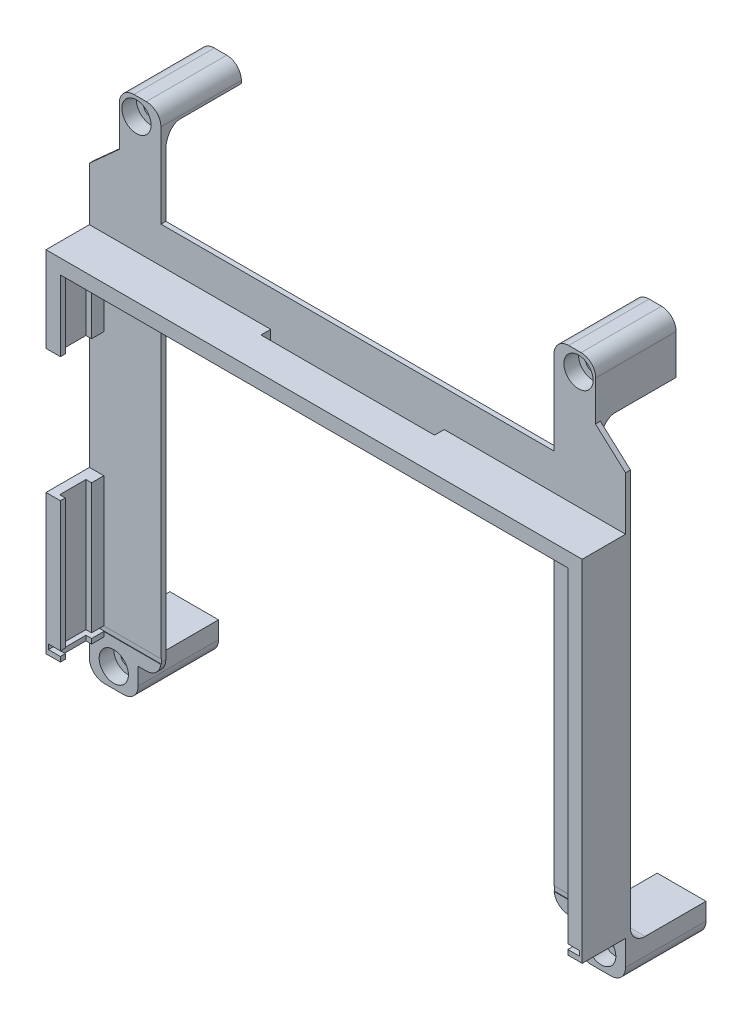
SolidWorks part; units mm, degrees
ref_plane "Front Plane" through (0, 0, 0) normal (1, 0, 0) x (0, 1, 0)
ref_plane "Top Plane" through (0, 0, 0) normal (0, 0, 1) x (0, 1, 0)
ref_plane "Right Plane" through (0, 0, 0) normal (0, 1, 0) x (-1, 0, 0)
sketch "Sketch1" plane through (0, 0, 0) normal (0, 0, 1) x (0, 1, 0)
  line L0 (-47.4715, -54.7542) -> (-54.0067, -54.7542)
  line L1 (-54.0067, -44.7542) -> (-54.0067, -54.7542)
  line L6 (-47.4715, -44.7542) -> (-54.0067, -44.7542)
  line L7 (-47.4715, -44.7542) -> (-47.4715, -54.7542)
  line L8 (42.478, -48.5761) -> (50.1367, -40.0774)
  line L9 (50.1367, -40.0774) -> (53.6912, -40.0774)
  line L10 (53.6912, -40.0774) -> (53.6912, -48.6408)
  line L11 (53.6912, -48.6408) -> (42.478, -48.5761)
  line L12 (53.6912, 49.1325) -> (42.478, 49.0678)
  line L13 (53.6912, 40.569) -> (53.6912, 49.1325)
  line L14 (50.1367, 40.569) -> (53.6912, 40.569)
  line L15 (42.478, 49.0678) -> (50.1367, 40.569)
  line L16 (-47.4715, 45.2458) -> (-47.4715, 55.2458)
  line L17 (-47.4715, 45.2458) -> (-54.0067, 45.2458)
  line L18 (-54.0067, 45.2458) -> (-54.0067, 55.2458)
  line L19 (-47.4715, 55.2458) -> (-54.0067, 55.2458)
  circle A0 centre (-50.0067, -49.7542) radius 1.6
  circle A1 centre (49.9933, -45.1018) radius 1.6
  circle A2 centre (49.9933, 45.5934) radius 1.6
  circle A3 centre (-50.0067, 50.2458) radius 1.6
extrude "Boss-Extrude1" add sketch "Sketch1" along normal blind 15.5
sketch "Sketch2" plane through (0, 0, 15.5) normal (0, 0, 1) x (1, 0, 0)
  line L0 (54.7542, -47.4715) -> (54.7542, -54.0067)
  line L1 (41.7542, -19.0067) -> (-42.2458, -19.0067) construction
  line L2 (-0.2458, -19.0067) -> (-0.2458, 62.4675) construction
  line L3 (-49.1325, 53.6912) -> (-49.0678, 42.478)
  line L4 (-40.569, 53.6912) -> (-49.1325, 53.6912)
  line L5 (44.7542, -54.0067) -> (54.7542, -54.0067)
  line L6 (44.7542, -47.4715) -> (44.7542, -54.0067)
  line L7 (40.0774, 53.6912) -> (40.0774, 33.4233)
  line L9 (-40.569, 53.6912) -> (-40.569, 33.4233)
  line L10 (-45.2458, -47.4715) -> (-40.569, -47.4715)
  line L11 (40.0774, 53.6912) -> (48.6408, 53.6912)
  line L12 (48.6408, 53.6912) -> (48.5761, 42.478)
  line L13 (-53.4458, -43.9132) -> (-53.4458, -44.8132)
  line L14 (-55.2458, -44.8132) -> (54.7542, -44.8132) construction
  line L15 (-45.2458, -47.4715) -> (-45.2458, -54.0067)
  line L16 (-45.2458, -54.0067) -> (-55.2458, -54.0067)
  line L17 (-55.2458, -47.4715) -> (-55.2458, -54.0067)
  line L18 (44.7542, -47.4715) -> (40.0774, -47.4715)
  line L19 (40.0774, -47.4715) -> (40.0774, 20.9868)
  line L20 (48.5761, 42.478) -> (54.7542, 36.9106)
  line L21 (54.7542, -47.4715) -> (54.7542, 36.9106)
  line L22 (40.0774, 20.9868) -> (-40.569, 20.9868)
  line L23 (40.0774, 33.4233) -> (-40.569, 33.4233)
  line L24 (-55.2458, -47.4715) -> (-55.2458, 36.9106)
  line L25 (-49.0678, 42.478) -> (-55.2458, 36.9106)
  line L26 (-40.569, -47.4715) -> (-40.569, 20.9868)
  line L27 (-52.317, -43.9132) -> (-52.317, -44.8132)
  line L28 (-49.1325, 53.6912) -> (-49.0678, 42.478)
  line L29 (-40.569, 53.6912) -> (-49.1325, 53.6912)
  line L31 (-53.4458, -43.9132) -> (52.9542, -43.9132) construction
  line L32 (52.9542, -43.9132) -> (52.9542, -44.8132)
  line L33 (-45.2458, -47.4715) -> (-45.2458, -54.0067)
  line L34 (-45.2458, -54.0067) -> (-55.2458, -54.0067)
  line L35 (-55.2458, -47.4715) -> (-55.2458, -54.0067)
  circle A0 centre (49.7542, -50.0067) radius 1.6
  circle A1 centre (45.1018, 49.9933) radius 1.6
  circle A2 centre (-45.5934, 49.9933) radius 1.6
  circle A3 centre (-50.2458, -50.0067) radius 1.6
  circle A4 centre (-45.5934, 49.9933) radius 1.6
  circle A5 centre (-50.2458, -50.0067) radius 1.6
  point P37 (-0.2458, 33.4233)
  point P38 (-0.2458, 20.9868)
  line M3 (48.5761, 42.478) -> (48.6408, 53.6912)
  line M4 (48.6408, 53.6912) -> (40.0774, 53.6912)
  line M5 (40.0774, 53.6912) -> (40.0774, 50.1367)
  line M6 (40.0774, 50.1367) -> (48.5761, 42.478)
  circle M7 centre (45.1018, 49.9933) radius 1.6
  dimension "D1" = 3.2
  dimension "D2" = 3.2
extrude "Boss-Extrude2" add sketch "Sketch2" along normal blind 1 contours L15 L26 L22 L19 L18 L6 L5 L0 L21 L20 L7 L23 L9 L4 L3 L25 L24 L17 L16 A2 A0 A3 M6 | M6 M3 M4 M5 M7 region at (53.2147, -50.7391, 15.5) region at (44.4212, 46.4122, 15.5)
sketch "Sketch3" plane through (0, 0, 16.5) normal (0, 0, 1) x (1, 0, 0)
  line L1 (-52.2958, 22.9868) -> (51.8042, 22.9868)
  line L2 (-52.2958, 22.9868) -> (-52.2958, 8.4399)
  line L3 (-52.2958, -42.8132) -> (-50.6497, -42.8132)
  line L4 (51.8042, 22.9868) -> (51.8042, -42.8132)
  line L5 (-52.2958, 22.9868) -> (51.8042, -42.8132) construction
  line L6 (-52.2958, -42.8132) -> (51.8042, 22.9868) construction
  line L20 (54.7542, 36.9106) -> (54.7542, -54.0067) construction
  line L21 (-55.2458, 25.9868) -> (54.7542, 25.9868)
  line L23 (40.0774, 20.9868) -> (-40.569, 20.9868) construction
  line L24 (-55.2458, 25.9868) -> (-55.2458, 8.4399)
  line L29 (-55.2458, -45.8132) -> (-52.2958, -45.8132)
  line L30 (54.7542, 25.9868) -> (54.7542, -45.8132)
  line L31 (-55.2458, 25.9868) -> (54.7542, -45.8132) construction
  line L32 (-55.2458, -45.8132) -> (54.7542, 25.9868) construction
  line L33 (-52.2958, -42.8132) -> (-52.2958, -45.8132)
  line L34 (51.8042, -42.8132) -> (51.8042, -45.8132)
  line L35 (51.8042, -45.8132) -> (54.7542, -45.8132)
  line L36 (50.1581, -42.8132) -> (51.8042, -42.8132)
  line L37 (-55.2458, 8.4399) -> (-52.2958, 8.4399)
  line L38 (-55.2458, -17.1408) -> (-52.2958, -17.1408)
  line L39 (-52.2958, -17.1408) -> (-52.2958, -42.8132)
  line L40 (-55.2458, -17.1408) -> (-55.2458, -45.8132)
  point P0 (-0.2458, -9.9132)
  point P5 (-0.2458, -9.9132)
  point P12 (-0.2458, -9.9132)
  point P20 (-0.2458, 20.9868)
  point P21 (-0.2458, -9.9132)
  line M14 (54.7542, -54.0067) -> (54.7542, 36.9106)
  line M24 (-55.2458, 36.9106) -> (-55.2458, -54.0067)
  dimension "D1" = 104.1
  dimension "D2" = 65.8
  dimension "D3" = 2
  dimension "D4" = 3
extrude "Boss-Extrude3" add sketch "Sketch3" along normal blind 2.5 contours L34 L35 L21 L29 L33 L2 L1 L4 M14 M24 | L33 L29 L40 L38 L39 region at (-53.6094, 15.7133, 16.5)
sketch "Sketch4" plane through (0, 0, 19) normal (0, 0, 1) x (1, 0, 0)
  line L0 (-0.2458, 22.9868) -> (-0.2458, -59.386) construction
  line L1 (-52.2958, 22.9868) -> (51.8042, 22.9868) construction
  line L2 (-55.2458, -45.8132) -> (54.7542, -45.8132) construction
  line L3 (-55.2458, 25.9868) -> (54.7542, 25.9868)
  line L4 (-55.2458, 25.9868) -> (-55.2458, 8.4399)
  line L5 (-55.2458, -45.8132) -> (-53.4458, -45.8132)
  line L6 (54.7542, 25.9868) -> (54.7542, -45.8132)
  line L7 (-55.2458, 25.9868) -> (54.7542, -45.8132) construction
  line L8 (-55.2458, -45.8132) -> (54.7542, 25.9868) construction
  line L9 (-53.4458, 24.0868) -> (52.9542, 24.0868)
  line L10 (-53.4458, 24.0868) -> (-53.4458, 8.4399)
  line L12 (52.9542, 24.0868) -> (52.9542, -43.9132)
  line L13 (-53.4458, 24.0868) -> (52.9542, -43.9132) construction
  line L14 (-53.4458, -43.9132) -> (52.9542, 24.0868) construction
  line L15 (-53.4458, -43.9132) -> (-53.4458, -45.8132)
  line L16 (52.9542, -43.9132) -> (52.9542, -45.8132)
  line L17 (52.9542, -45.8132) -> (54.7542, -45.8132)
  line L18 (-55.2458, 8.4399) -> (-53.4458, 8.4399)
  line L19 (-55.2458, 8.4399) -> (-52.2958, 8.4399) construction
  line L20 (-55.2458, -17.1408) -> (-53.4458, -17.1408)
  line L21 (-55.2458, -17.1408) -> (-52.2958, -17.1408) construction
  line L22 (-55.2458, -17.1408) -> (-55.2458, -45.8132)
  line L23 (-53.4458, -17.1408) -> (-53.4458, -43.9132)
  line L24 (-55.2458, -43.8132) -> (54.7542, -43.8132) construction
  point P4 (-0.2458, -9.9132)
  point P13 (-0.2458, -9.9132)
  dimension "D1" = 106.4
  dimension "D2" = 68
  dimension "D3" = 67.9
extrude "Boss-Extrude4" add sketch "Sketch4" along normal blind 5.4
sketch "Sketch5" plane through (0, 0, 24.4) normal (0, 0, 1) x (1, 0, 0)
  line L0 (-55.2458, 8.4399) -> (-52.2958, 8.4399)
  line L1 (-52.2958, 22.9868) -> (51.8042, 22.9868)
  line L2 (-52.2958, 22.9868) -> (-52.2958, 8.4399)
  line L4 (51.8042, 22.9868) -> (51.8042, -45.8132)
  line L5 (-55.2458, 25.9868) -> (54.7542, 25.9868)
  line L6 (-55.2458, 25.9868) -> (-55.2458, 8.4399)
  line L7 (-55.2458, -45.8132) -> (-52.2958, -45.8132)
  line L8 (54.7542, 25.9868) -> (54.7542, -45.8132)
  line L9 (-55.2458, -17.1408) -> (-52.2958, -17.1408)
  line L10 (51.8042, -45.8132) -> (54.7542, -45.8132)
  line L11 (-52.2958, -17.1408) -> (-52.2958, -45.8132)
  line L12 (-55.2458, -17.1408) -> (-55.2458, -45.8132)
extrude "Boss-Extrude5" add sketch "Sketch5" along normal blind 1
sketch "Sketch7" plane through (0, 0, 25.4) normal (0, 0, 1) x (1, 0, 0)
  line L0 (-54.7458, -43.8132) -> (54.2542, -43.8132)
  line L1 (54.2542, -43.8132) -> (54.2542, -44.8132)
  line L2 (54.2542, -44.8132) -> (-54.7458, -44.8132)
  line L3 (-54.7458, -44.8132) -> (-54.7458, -43.8132)
  line L4 (51.8042, -45.8132) -> (54.7542, -45.8132) construction
  line L5 (54.7542, -45.8132) -> (54.7542, 25.9868) construction
  line L6 (-55.2458, -17.1408) -> (-55.2458, -45.8132) construction
  dimension "D1" = 1
  dimension "D2" = 1
  dimension "D3" = 0.5
  dimension "D4" = 0.5
extrude "Cut-Extrude1" cut sketch "Sketch7" against normal blind 9
fillet "Fillet1" radius 3 10 edges at (48.6408, 53.6912, 8.25) (-49.1325, 53.6912, 8.25) (-40.569, -47.4715, 16) (-55.2458, -54.0067, 8.25) (-45.2458, -54.0067, 8.25) (40.0774, -47.4715, 16) (44.7542, -54.0067, 8.25) (54.7542, -54.0067, 8.25) (40.0774, 53.6912, 8.25) (-40.569, 53.6912, 8.25)
fillet "Fillet2" radius 3 4 edges at (-50.2458, -47.4715, 15.5) (-44.8184, 46.3073, 15.5) (44.3268, 46.3073, 15.5) (49.7542, -47.4715, 15.5)
sketch "Sketch8" plane through (0, 25.9868, 0) normal (0, 1, 0) x (-1, 0, 0)
  line L0 (-40.0774, 16.5) -> (40.569, 16.5) construction
  line L1 (-17.5542, 16.5) -> (18.0458, 16.5)
  line L2 (-17.5542, 16.5) -> (-17.5542, 18.5)
  line L3 (-17.5542, 18.5) -> (18.0458, 18.5)
  line L4 (18.0458, 16.5) -> (18.0458, 18.5)
  line L5 (0.2458, 25.4) -> (0.2458, 15.5) construction
  line L6 (-54.7542, 25.4) -> (55.2458, 25.4) construction
  line L7 (-40.0774, 15.5) -> (40.569, 15.5) construction
  dimension "D1" = 2
  dimension "D2" = 17.8
  dimension "D3" = 17.8
extrude "Cut-Extrude2" cut sketch "Sketch8" against normal blind 2
sketch "Sketch9" plane through (0, 0, 16.5) normal (0, 0, 1) x (1, 0, 0)
  line L0 (-0.2458, 20.9868) -> (-0.2458, 55.7211) construction
  line L1 (40.0774, 20.9868) -> (-40.569, 20.9868) construction
  circle A0 centre (-45.5934, 49.9933) radius 3
  circle A2 centre (-50.2458, -50.0067) radius 3
  circle A3 centre (49.7542, -50.0067) radius 3
  circle A4 centre (45.1018, 49.9933) radius 3
  dimension "D1" = 6
  dimension "D2" = 6
extrude "Cut-Extrude3" cut sketch "Sketch9" against normal blind 3
